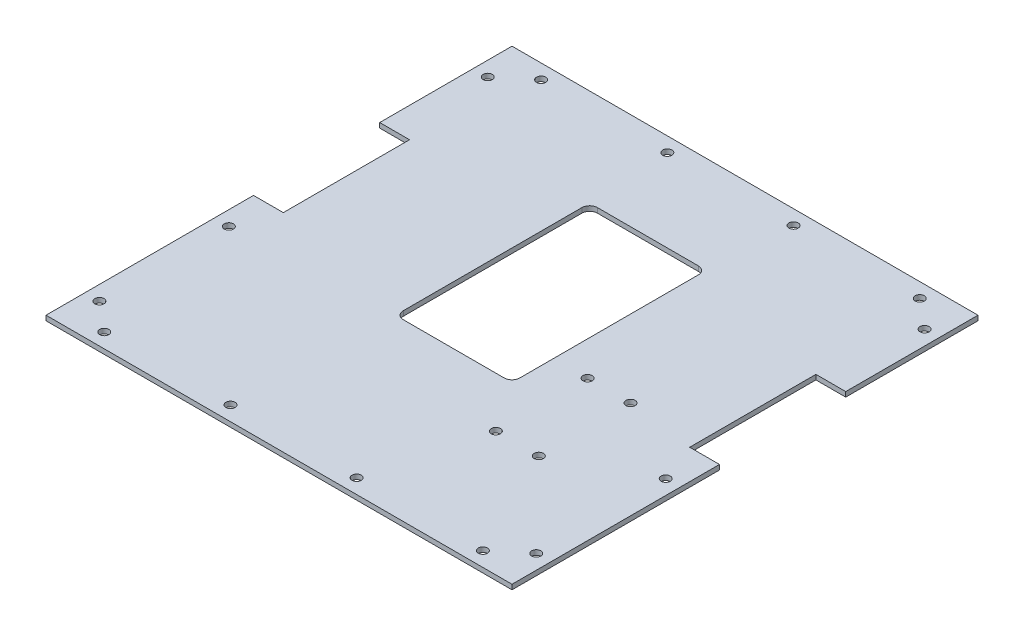
SolidWorks part; units mm, degrees
material "Thornel VCB-20 Carbon Cloth"
ref_plane "Front Plane" through (0, 0, 0) normal (0, 0, 1) x (1, 0, 0)
ref_plane "Top Plane" through (0, 0, 0) normal (0, 1, 0) x (1, 0, 0)
ref_plane "Right Plane" through (0, 0, 0) normal (1, 0, 0) x (0, 0, -1)
sketch "Sketch2" plane through (0, 0, 0) normal (0, 1, 0) x (1, 0, 0)
  line L0 (0, 0) -> (152.4, 0)
  line L1 (152.4, 0) -> (152.4, 152.4)
  line L2 (152.4, 152.4) -> (0, 152.4)
  line L3 (0, 152.4) -> (0, 0)
  dimension "D1" = 152.4
  dimension "D2" = 152.4
extrude "Boss-Extrude1" add sketch "Sketch2" along normal blind 1.5875
sketch "Sketch3" plane through (0, 1.5875, 0) normal (0, 1, 0) x (1, 0, 0)
  line L0 (0, 152.4) -> (4.7625, 152.4)
  line L1 (152.4, 152.4) -> (0, 152.4) construction
  line L2 (4.7625, 152.4) -> (4.7625, 0)
  line L3 (0, 0) -> (152.4, 0) construction
  line L4 (0, 152.4) -> (0, 147.6375)
  line L5 (0, 152.4) -> (0, 0) construction
  line L6 (0, 147.6375) -> (152.4, 147.6375)
  line L7 (152.4, 0) -> (152.4, 152.4) construction
  line L8 (152.4, 152.4) -> (147.6375, 152.4)
  line L9 (147.6375, 152.4) -> (147.6375, 0)
  line L10 (152.4, 0) -> (152.4, 4.7625)
  line L11 (152.4, 4.7625) -> (0, 4.7625)
  point P21 (4.7625, 139.7)
  point P23 (14.2875, 147.6375)
  point P24 (147.6375, 139.7)
  point P25 (138.1125, 4.7625)
  point P26 (4.7625, 12.7)
  dimension "D1" = 4.7625
  dimension "D2" = 4.7625
  dimension "D3" = 4.7625
  dimension "D4" = 4.7625
  dimension "D5" = 12.7
  dimension "D6" = 14.2875
  dimension "D7" = 12.7
  dimension "D8" = 14.2875
  dimension "D9" = 12.7
sketch "Sketch4" plane through (0, 1.5875, 0) normal (0, 1, 0) x (1, 0, 0)
  point P0 (14.2875, 147.6375)
  point P3 (147.6375, 139.7)
  point P6 (138.1125, 4.7625)
  point P9 (4.7625, 12.7)
sketch "Sketch6" plane through (0, 1.5875, 0) normal (0, 1, 0) x (1, 0, 0)
  line L0 (152.4, 4.7625) -> (0, 4.7625) construction
  line L1 (0, 152.4) -> (0, 0) construction
  point P0 (14.2875, 147.6375)
  point P3 (14.2875, 4.7625)
  dimension "D1" = 14.2875
hole_wizard "Ø3.0mm Dowel Hole1" positions "Sketch6" profile "Sketch7" hole size "Ø3.0" standard "ANSI Metric" end condition through all
sketch "Sketch7" plane through (14.2875, 1.5875, -147.6375) normal (1, 0, 0) x (0, 0, 1)
  line L0 (0, 0) -> (0, 1.5875)
  line L1 (0, 1.5875) -> (1.5, 1.5875)
  line L2 (1.5, 1.5875) -> (1.5, 0)
  line L5 (1.5, 0) -> (0, 0)
  line L11 (0, -6.35) -> (0, 107.95) construction
  dimension "Thru Hole Dia." = 3
  dimension "Thru Hole Depth" = 1.5875
sketch "Sketch8" plane through (0, 1.5875, 0) normal (0, 1, 0) x (1, 0, 0)
  point P0 (4.7625, 139.7)
  point P3 (147.6375, 139.7)
hole_wizard "Ø3.0mm Dowel Hole2" positions "Sketch8" profile "Sketch9" hole size "Ø3.0" standard "ANSI Metric" end condition through all
sketch "Sketch9" plane through (4.7625, 1.5875, -139.7) normal (1, 0, 0) x (0, 0, 1)
  line L0 (0, 0) -> (0, 1.5875)
  line L1 (0, 1.5875) -> (1.5, 1.5875)
  line L2 (1.5, 1.5875) -> (1.5, 0)
  line L5 (1.5, 0) -> (0, 0)
  line L11 (0, -6.35) -> (0, 107.95) construction
  dimension "Thru Hole Dia." = 3
  dimension "Thru Hole Depth" = 1.5875
pattern_linear "LPattern1" count 4 spacing 42.3333 along (0, 0, 1) skipping (1, 0) of "Ø3.0mm Dowel Hole2"
pattern_linear "LPattern2" count 4 spacing 41.275 along (1, 0, 0) of "Ø3.0mm Dowel Hole1"
sketch "Sketch12" plane through (0, 1.5875, 0) normal (0, 1, 0) x (1, 0, 0)
  line L10 (0, 152.4) -> (0, 0) construction
  line L11 (57.15, 120.65) -> (95.25, 120.65)
  line L12 (57.15, 120.65) -> (57.15, 57.15)
  line L13 (57.15, 57.15) -> (95.25, 57.15)
  line L14 (95.25, 120.65) -> (95.25, 57.15)
  line L15 (152.4, 152.4) -> (0, 152.4) construction
  line L16 (152.4, 0) -> (152.4, 152.4) construction
  dimension "D1" = 57.15
  dimension "D2" = 31.75
  dimension "D3" = 57.15
  dimension "D4" = 63.5
extrude "Cut-Extrude1" cut sketch "Sketch12" against normal blind 2.54 contours L14 L12 region at (76.2, 1.5875, -88.9)
fillet "Fillet2" radius 2.54 4 edges at (95.25, 0.7937, -57.15) (57.15, 0.7937, -57.15) (57.15, 0.7937, -120.65) (95.25, 0.7937, -120.65)
sketch "Sketch13" plane through (0, 1.5875, 0) normal (0, 1, 0) x (1, 0, 0)
  line L0 (152.4, 0) -> (152.4, 152.4) construction
  line L1 (152.4, 109.14) -> (142.65, 109.14)
  line L2 (152.4, 109.14) -> (152.4, 67.86)
  line L3 (152.4, 67.86) -> (142.65, 67.86)
  line L4 (142.65, 109.14) -> (142.65, 67.86)
  line L5 (152.4, 152.4) -> (0, 152.4) construction
  line L6 (76.2, 152.4) -> (76.2, 0) construction
  line L7 (0, 0) -> (152.4, 0) construction
  line L8 (0, 67.86) -> (9.75, 67.86)
  line L9 (9.75, 109.14) -> (9.75, 67.86)
  line L10 (0, 109.14) -> (9.75, 109.14)
  line L11 (0, 109.14) -> (0, 67.86)
  point P8 (147.525, 67.86)
  dimension "D1" = 43.26
  dimension "D2" = 41.28
  dimension "D3" = 9.75
extrude "Cut-Extrude2" cut sketch "Sketch13" against normal through all
sketch "Sketch14" plane through (0, 0, 0) normal (0, -1, 0) x (1, 0, 0)
  circle A0 centre (120.4506, -70.7194) radius 1.5
  circle A1 centre (106.4006, -70.7194) radius 1.5
  circle A2 centre (120.4506, -40.7194) radius 1.5
  circle A3 centre (106.4006, -40.7194) radius 1.5
extrude "Cut-Extrude3" cut sketch "Sketch14" against normal blind 10 contours A2 | A3 | A1 | A0 region at (120.4506, 0, -70.7194) region at (106.4006, 0, -70.7194) region at (120.4506, 0, -40.7194) region at (106.4006, 0, -40.7194)
